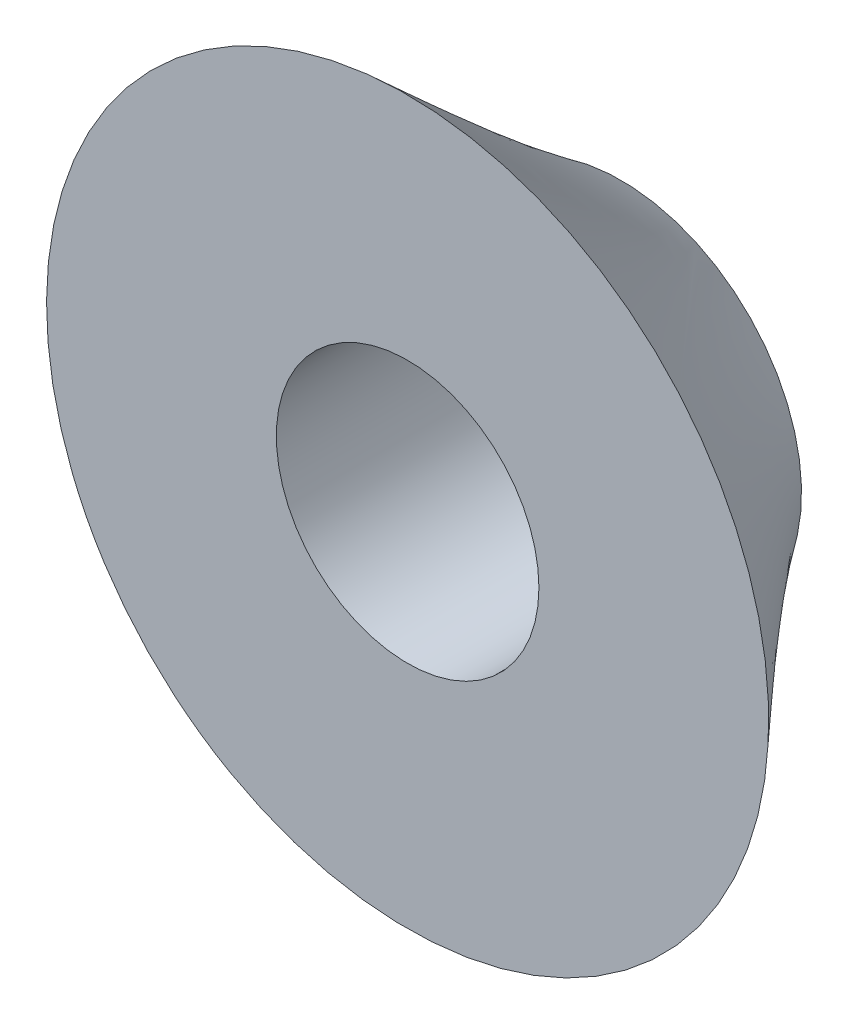
SolidWorks part; units mm, degrees
ref_plane "Plano frontal" through (0, 0, 0) normal (0, 0, 1) x (1, 0, 0)
ref_plane "Plano superior" through (0, 0, 0) normal (0, 1, 0) x (1, 0, 0)
ref_plane "Plano direito" through (0, 0, 0) normal (1, 0, 0) x (0, 0, -1)
sketch "Esboço1" plane through (0, 0, 0) normal (0, 0, 1) x (1, 0, 0)
  circle A1 centre (0, 0) radius 5.5
  dimension "D2" = 11
ref_plane "Plano1" through (0, 0, 6.5) normal (0, 0, 1) x (1, 0, 0)
sketch "Esboço2" plane through (0, 0, 6.5) normal (0, 0, 1) x (1, 0, 0)
  circle A0 centre (0, 0) radius 11
  dimension "D1" = 22
loft "Loft2" add profiles "Esboço1", "Esboço2" connector at (2.2948, 4.9984, 0) connector at (8.274, 7.2485, 6.5)
sketch "Esboço3" plane through (0, 0, 0) normal (0, 0, 1) x (1, 0, 0)
  circle A0 centre (0, 0) radius 4
  dimension "D1" = 8
extrude "Corte-extrusão1" cut sketch "Esboço3" against normal through all both and the other way through all
